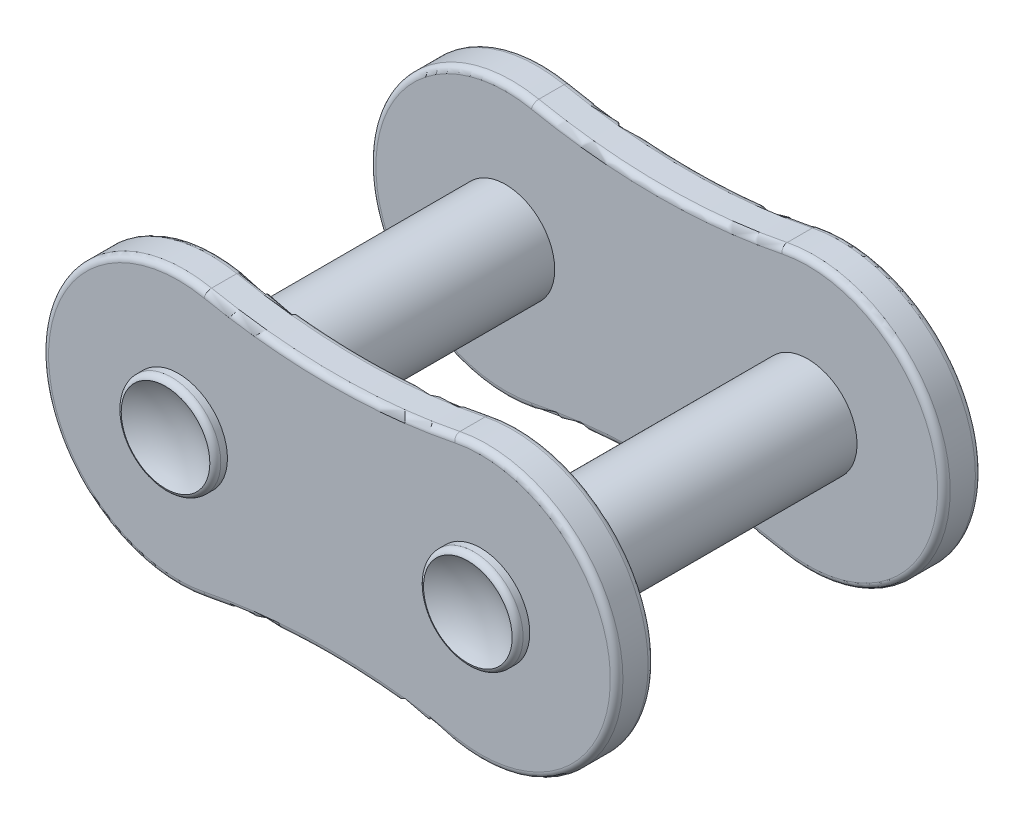
SolidWorks part; units mm, degrees
ref_plane "Front Plane" through (0, 0, 0) normal (0, 0, 1) x (1, 0, 0)
ref_plane "Top Plane" through (0, 0, 0) normal (0, 1, 0) x (1, 0, 0)
ref_plane "Right Plane" through (0, 0, 0) normal (1, 0, 0) x (0, 0, -1)
sketch "Sketch1" plane through (0, 0, 0) normal (0, 0, 1) x (1, 0, 0)
  line L0 (6, 0) -> (-6, 0) construction
  line L1 (0, 0) -> (0, 4.7987) construction
  circle A0 centre (-6, 0) radius 1.95
  arc A1 (-4.9284, 5.2926) -> (-4.9284, -5.2926) centre (-6, 0) ccw
  arc A2 (4.9284, 5.2926) -> (4.9284, -5.2926) centre (6, 0) cw
  circle A3 centre (6, 0) radius 1.95
  arc A4 (-4.9284, 5.2926) -> (4.9284, 5.2926) centre (0, 29.6344) ccw
  arc A5 (-4.9284, -5.2926) -> (4.9284, -5.2926) centre (0, -29.6344) cw
  dimension "D1" = 3.9
  dimension "D2" = 10.8
  dimension "D4" = 24.8357
  dimension "D3" = 6
extrude "Boss-Extrude1" add sketch "Sketch1" along normal blind 1.5
sketch "Sketch2" plane through (0, 0, 0) normal (0, 0, 1) x (1, 0, 0)
  circle A0 centre (-6, 0) radius 1.95 construction
  circle A1 centre (-6, 0) radius 1.95
extrude "Boss-Extrude2" add sketch "Sketch2" along normal blind 15 and the other way blind 0.508
ref_plane "Plane1" through (0, 0, 7.246) normal (0, 0, 1) x (1, 0, 0)
mirror "Mirror1" about plane through (0, 0, 7.246) normal (0, 0, 1) of "Boss-Extrude1"
sketch "Sketch3" plane through (0, 0, 0) normal (0, 1, 0) x (1, 0, 0)
  line L0 (-6, -14.492) -> (-6, -15.252) construction
  line L1 (-7.95, -15) -> (-4.05, -15) construction
  line L2 (-7.95, -14.492) -> (-4.05, -14.492) construction
  line L3 (-7.7592, -15) -> (-6, -15)
  line L4 (-6, -14.492) -> (-6, -15)
  arc A0 (-6, -14.492) -> (-7.7592, -15) centre (-6, -17.792) ccw
  dimension "D2" = 3.3
  dimension "D1" = 0.76
revolve "Cut-Revolve3" cut sketch "Sketch3" angle 360 about L0
mirror "Mirror4" about plane through (0, 0, 7.246) normal (0, 0, 1) of "Cut-Revolve3"
mirror "Mirror2" about plane through (0, 0, 0) normal (1, 0, 0) of "Mirror4", "Cut-Revolve3", "Boss-Extrude2"
fillet "Fillet1" radius 0.25 16 edges at (11.4, 0, 0) (0, -4.7987, 0) (-11.4, 0, 0) (11.4, 0, 1.5) (0, -4.7987, 1.5) (-11.4, 0, 1.5) (11.4, 0, 12.992) (0, -4.7987, 12.992) (-11.4, 0, 12.992) (11.4, 0, 14.492) (0, -4.7987, 14.492) (-11.4, 0, 14.492) (0, 4.7987, 0) (0, 4.7987, 1.5) (0, 4.7987, 12.992) (0, 4.7987, 14.492)
fillet "Fillet2" radius 0.25 4 edges at (4.05, 0, -0.508) (-4.05, 0, -0.508) (-4.05, 0, 15) (4.05, 0, 15)
scale "Scale1" scale about centroid uniform scaling yes scale factor 0.5
